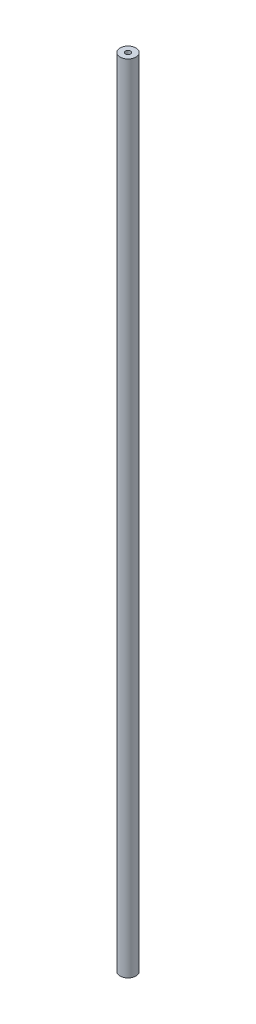
SolidWorks part; units mm, degrees
material "6061-T6 (SS)"
ref_plane "Front Plane" through (0, 0, 0) normal (0, 0, 1) x (1, 0, 0)
ref_plane "Top Plane" through (0, 0, 0) normal (0, 1, 0) x (1, 0, 0)
ref_plane "Right Plane" through (0, 0, 0) normal (1, 0, 0) x (0, 0, -1)
sketch "Sketch1" plane through (0, 0, 0) normal (0, 1, 0) x (1, 0, 0)
  circle A0 centre (0, 0) radius 6.35
  dimension "D1" = 12.7
extrude "Boss-Extrude1" add sketch "Sketch1" along normal blind 635
hole_wizard "#10-32 Tapped Hole1" positions "Sketch2" profile "Sketch4" tap size "#10-32" standard "ANSI Inch"
sketch "Sketch2" plane through (0, 0, 0) normal (0, -1, 0) x (-1, 0, 0)
  point P0 (0, 0)
sketch "Sketch4" plane through (0, 0, 0) normal (1, 0, 0) x (0, 0, -1)
  line L0 (0, 0) -> (0, 13.2428)
  line L1 (0, 13.2428) -> (2.0193, 12.0294)
  line L2 (2.0193, 12.0294) -> (2.0193, 0)
  line L5 (2.0193, 0) -> (0, 0)
  line L10 (0, 13.2428) -> (-2.0193, 12.0294) construction
  line L11 (0, -6.35) -> (0, 107.95) construction
  dimension "Tap Drill Dia." = 4.0386
  dimension "Tap Drill Depth" = 12.0294
  dimension "Drill Angle" = 118
cosmetic thread "Hole Thread1"
hole_wizard "#10-32 Tapped Hole2" positions "Sketch5" profile "Sketch6" tap size "#10-32" standard "ANSI Inch"
sketch "Sketch5" plane through (0, 635, 0) normal (0, 1, 0) x (1, 0, 0)
  point P0 (0, 0)
sketch "Sketch6" plane through (0, 635, 0) normal (1, 0, 0) x (0, 0, 1)
  line L0 (0, 0) -> (0, 13.2428)
  line L1 (0, 13.2428) -> (2.0193, 12.0294)
  line L2 (2.0193, 12.0294) -> (2.0193, 0)
  line L5 (2.0193, 0) -> (0, 0)
  line L10 (0, 13.2428) -> (-2.0193, 12.0294) construction
  line L11 (0, -6.35) -> (0, 107.95) construction
  dimension "Tap Drill Dia." = 4.0386
  dimension "Tap Drill Depth" = 12.0294
  dimension "Drill Angle" = 118
cosmetic thread "Hole Thread2" parameters "D1"=9.652, "D2"=4.826
